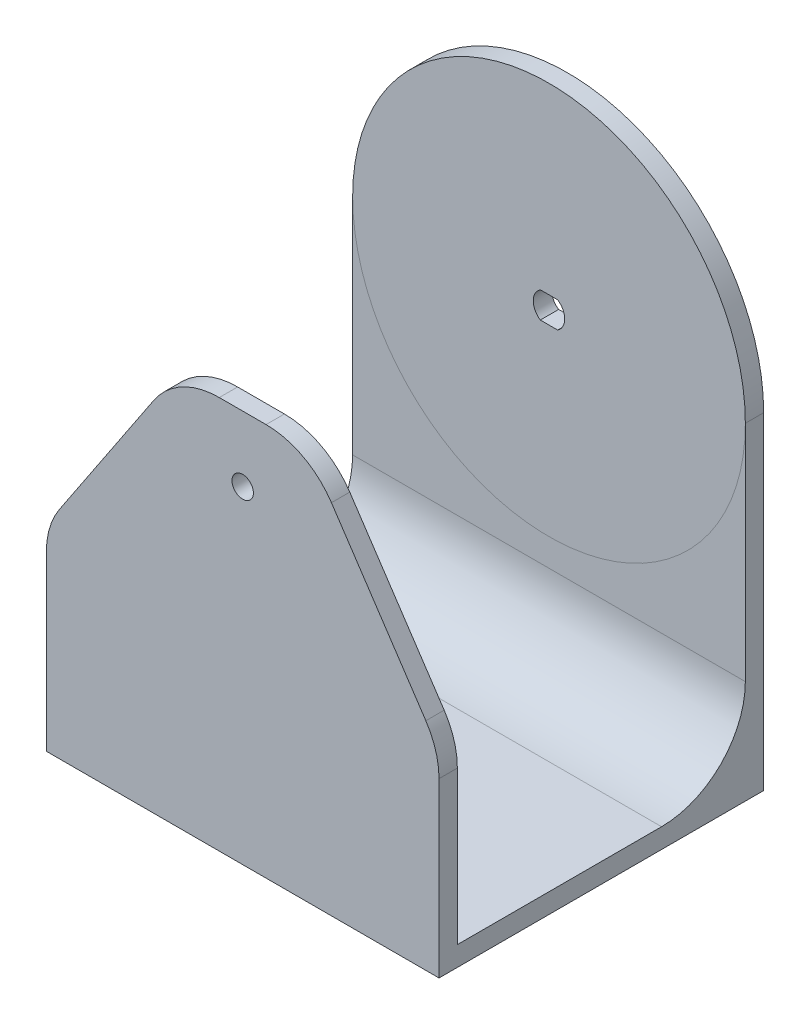
SolidWorks part; units mm, degrees
material "PETG"
ref_plane "Front Plane" through (0, 0, 0) normal (0, 0, 1) x (1, 0, 0)
ref_plane "Top Plane" through (0, 0, 0) normal (0, 1, 0) x (1, 0, 0)
ref_plane "Right Plane" through (0, 0, 0) normal (1, 0, 0) x (0, 0, -1)
sketch "Sketch2" plane through (0, 0, 0) normal (0, 0, 1) x (1, 0, 0)
  line L0 (3.3166, 5) -> (-3.3166, 5)
  line L1 (3.3166, -5) -> (-3.3166, -5)
  circle A0 centre (0, 0) radius 75
  circle A1 centre (0, 0) radius 6
  dimension "D1" = 150
  dimension "D2" = 12
  dimension "D3" = 10
extrude "Boss-Extrude1" add sketch "Sketch2" along normal mid plane 7 contours A0 A1 | L0 A1 | L1 A1 region at (0, 5.403, 0) region at (0, -5.403, 0) region at (-72.8787, 0, 0)
sketch "Sketch8" plane through (0, 0, 3.5) normal (0, 0, 1) x (1, 0, 0)
  line L0 (-75, 0) -> (-75, -125)
  line L1 (-75, -125) -> (75, -125)
  line L2 (75, -125) -> (75, 0)
  circle A0 centre (0, 0) radius 75 construction
  arc A1 (-75, 0) -> (75, 0) centre (0, 0) ccw
extrude "Boss-Extrude2" add sketch "Sketch8" against normal blind 7 separate body contours A1 L0 L1 | A1 L1 L2 | L2 L1 L0 A1 region at (0, -89.8326, 3.5)
sketch "Sketch11" plane through (0, 0, 3.5) normal (0, 0, 1) x (1, 0, 0)
  line L0 (75, -125) -> (75, 0) construction
  line L1 (-75, -125) -> (75, -125)
  line L2 (-75, -125) -> (-75, -117.4557)
  line L3 (-75, -117.4557) -> (75, -117.4557)
  line L4 (75, -125) -> (75, -117.4557)
extrude "Boss-Extrude4" add sketch "Sketch11" along normal blind 110
sketch "Sketch12" plane through (0, 0, 113.5) normal (0, 0, 1) x (1, 0, 0)
  line L1 (-75, -125) -> (75, -125)
  line L2 (-75, -125) -> (-75, 25.0443)
  line L3 (-75, 25.0443) -> (75, 25.0443)
  line L4 (75, -125) -> (75, 25.0443)
extrude "Boss-Extrude5" add sketch "Sketch12" along normal blind 7
sketch "Sketch13" plane through (0, 0, 120.5) normal (0, 0, 1) x (1, 0, 0)
  line L0 (0, -125) -> (0, 0) construction
  line L1 (-75, -125) -> (75, -125) construction
  circle A0 centre (0, 0) radius 4.1
extrude "Cut-Extrude3" cut sketch "Sketch13" against normal blind 7
fillet "Fillet1" radius 32 1 edges at (0, -117.4557, 3.5)
sketch "Sketch14" plane through (0, 0, 120.5) normal (0, 0, 1) x (1, 0, 0)
  line L0 (-75, -125) -> (-75, -49.9778) construction
  line L1 (-75, 25.0443) -> (-75, -125) construction
  line L2 (0, 25.0443) -> (-25, 25.0443) construction
  line L3 (75, 25.0443) -> (-75, 25.0443) construction
  line L4 (-75, -49.9778) -> (-25, 25.0443)
  line L5 (-25, 25.0443) -> (-75, 25.0443)
  line L6 (-75, 25.0443) -> (-75, -49.9778)
extrude "Cut-Extrude4" cut sketch "Sketch14" against normal blind 7
sketch "Sketch16" plane through (0, 0, 120.5) normal (0, 0, 1) x (1, 0, 0)
  line L0 (75, -125) -> (75, -49.9778) construction
  line L1 (75, -125) -> (75, 25.0443) construction
  line L2 (0, 25.0443) -> (25, 25.0443) construction
  line L3 (75, 25.0443) -> (-25, 25.0443) construction
  line L4 (25, 25.0443) -> (75, -49.9778)
  line L5 (75, -49.9778) -> (75, 25.0443)
  line L6 (25, 25.0443) -> (75, 25.0443)
extrude "Cut-Extrude5" cut sketch "Sketch16" against normal blind 7
fillet "Fillet2" radius 30 1 edges at (-25, 25.0443, 117)
fillet "Fillet3" radius 30 1 edges at (25, 25.0443, 117)
fillet "Fillet4" radius 30 1 edges at (-75, -49.9778, 117)
fillet "Fillet5" radius 30 1 edges at (75, -49.9778, 117)
